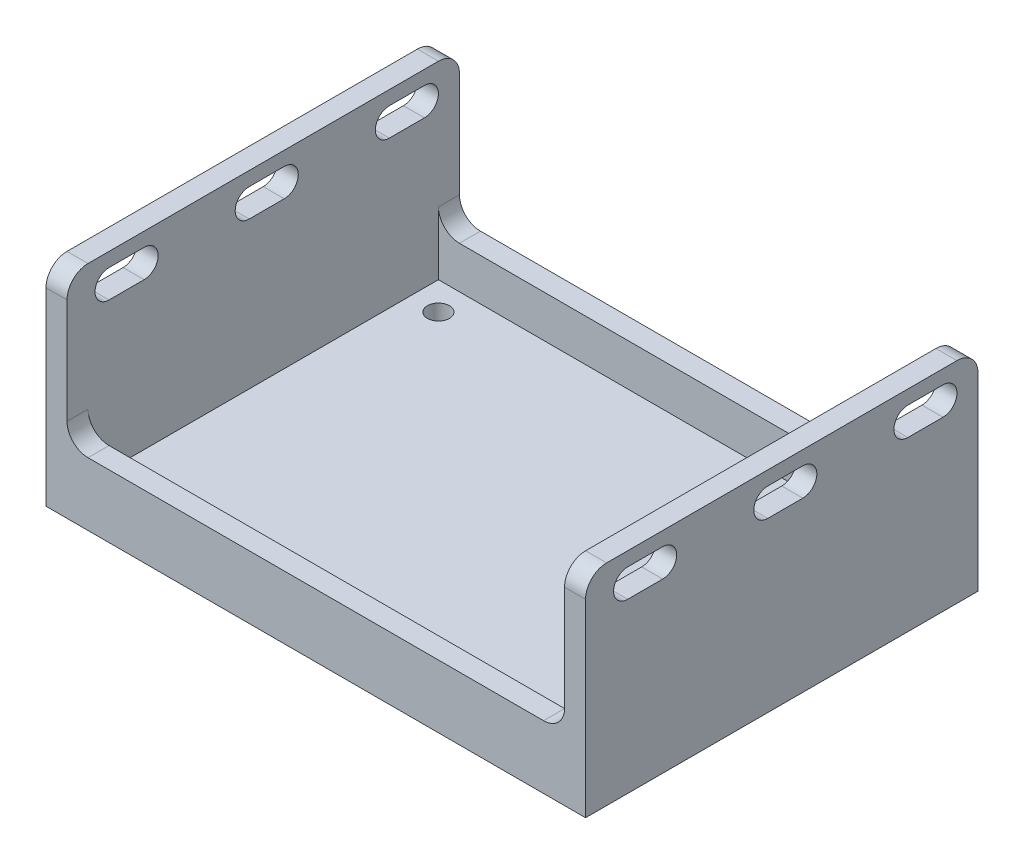
SolidWorks part; units mm, degrees
ref_plane "Front Plane" through (0, 0, 0) normal (0, 0, 1) x (1, 0, 0)
ref_plane "Top Plane" through (0, 0, 0) normal (0, 1, 0) x (1, 0, 0)
ref_plane "Right Plane" through (0, 0, 0) normal (1, 0, 0) x (0, 0, -1)
sketch "Sketch1" plane through (0, 0, 0) normal (0, 1, 0) x (1, 0, 0)
  line L1 (35.5, 25) -> (-35.5, 25)
  line L2 (35.5, 25) -> (35.5, -25)
  line L3 (35.5, -25) -> (-35.5, -25)
  line L4 (-35.5, 25) -> (-35.5, -25)
  line L5 (0, -25) -> (0, 25) construction
  line L6 (35.5, 0) -> (-35.5, 0) construction
  line L7 (31.5, 21) -> (-31.5, 21) construction
  line L8 (31.5, 21) -> (31.5, -21) construction
  line L9 (31.5, -21) -> (-31.5, -21) construction
  line L10 (-31.5, 21) -> (-31.5, -21) construction
  line L11 (0, -21) -> (0, 21) construction
  line L12 (31.5, 0) -> (-31.5, 0) construction
  circle A0 centre (-31.5, 21) radius 1.575
  circle A1 centre (31.5, 21) radius 1.575
  circle A2 centre (31.5, -21) radius 1.575
  circle A3 centre (-31.5, -21) radius 1.575
  point P0 (0, 0)
  point P4 (0, 0)
  dimension "D5" = 3.15
  dimension "D1" = 50
  dimension "D2" = 71
  dimension "D3" = 42
  dimension "D4" = 63
extrude "Boss-Extrude1" add sketch "Sketch1" along normal blind 3
sketch "Sketch2" plane through (0, 0, 0) normal (0, 1, 0) x (1, 0, 0)
  line L8 (-38.5, 28) -> (-38.5, -28)
  line L9 (-38.5, -28) -> (38.5, -28)
  line L10 (38.5, -28) -> (38.5, 28)
  line L11 (38.5, 28) -> (-38.5, 28)
  line L12 (-38.5, 28) -> (-38.5, -28)
  line L13 (-38.5, -28) -> (38.5, -28)
  line L14 (38.5, -28) -> (38.5, 28)
  line L15 (38.5, 28) -> (-38.5, 28)
  line L16 (-35.5, 25) -> (-35.5, -25)
  line L17 (-35.5, -25) -> (35.5, -25)
  line L18 (35.5, -25) -> (35.5, 25)
  line L19 (35.5, 25) -> (-35.5, 25)
  line L20 (-35.5, 25) -> (-35.5, -25)
  line L21 (-35.5, -25) -> (35.5, -25)
  line L22 (35.5, -25) -> (35.5, 25)
  line L23 (35.5, 25) -> (-35.5, 25)
  dimension "D1" = 3
  dimension "D2" = 0
extrude "Boss-Extrude2" add sketch "Sketch2" along normal blind 30
sketch "Sketch3" plane through (0, 0, -28) normal (0, 0, -1) x (-1, 0, 0)
  line L1 (-38.5, 30) -> (-38.5, 0) construction
  line L2 (-35.5, 39) -> (35.5, 39)
  line L3 (-35.5, 39) -> (-35.5, 9)
  line L4 (-35.5, 9) -> (35.5, 9)
  line L5 (35.5, 39) -> (35.5, 9)
  line L6 (38.5, 30) -> (38.5, 0) construction
  dimension "D1" = 9
  dimension "D2" = 3
  dimension "D3" = 3
  dimension "D4" = 30
extrude "Cut-Extrude1" cut sketch "Sketch3" against normal through all
sketch "Sketch4" plane through (-38.5, 0, 0) normal (-1, 0, 0) x (0, 0, 1)
  line L0 (-20.5, 26) -> (-20.5, 30) construction
  line L1 (-28, 30) -> (28, 30) construction
  line L2 (-18, 26) -> (-23, 26) construction
  line L3 (-18, 24) -> (-23, 24)
  line L4 (-18, 28) -> (-23, 28)
  line L5 (-23, 26) -> (-28, 26) construction
  line L6 (-28, 30) -> (-28, 0) construction
  line L7 (2, 28) -> (-3, 28)
  line L8 (2, 24) -> (-3, 24)
  line L9 (2, 26) -> (-3, 26) construction
  line L10 (22, 28) -> (17, 28)
  line L11 (22, 24) -> (17, 24)
  line L12 (22, 26) -> (17, 26) construction
  arc A0 (-18, 24) -> (-18, 28) centre (-18, 26) ccw
  arc A1 (-23, 28) -> (-23, 24) centre (-23, 26) ccw
  arc A2 (2, 24) -> (2, 28) centre (2, 26) ccw
  arc A3 (-3, 28) -> (-3, 24) centre (-3, 26) ccw
  arc A4 (22, 24) -> (22, 28) centre (22, 26) ccw
  arc A5 (17, 28) -> (17, 24) centre (17, 26) ccw
  point P7 (-20.5, 26)
  point P20 (-0.5, 26)
  point P27 (19.5, 26)
  dimension "D3" = 2
  dimension "D1" = 5
  dimension "D2" = 5
  dimension "D4" = 4
  dimension "D5" = 3
extrude "Cut-Extrude2" cut sketch "Sketch4" against normal through all
fillet "Fillet1" radius 3 8 edges at (-37, 30, 28) (-37, 30, -28) (37, 30, 28) (37, 30, -28) (-35.5, 9, -26.5) (-35.5, 9, 26.5) (35.5, 9, 26.5) (35.5, 9, -26.5)
